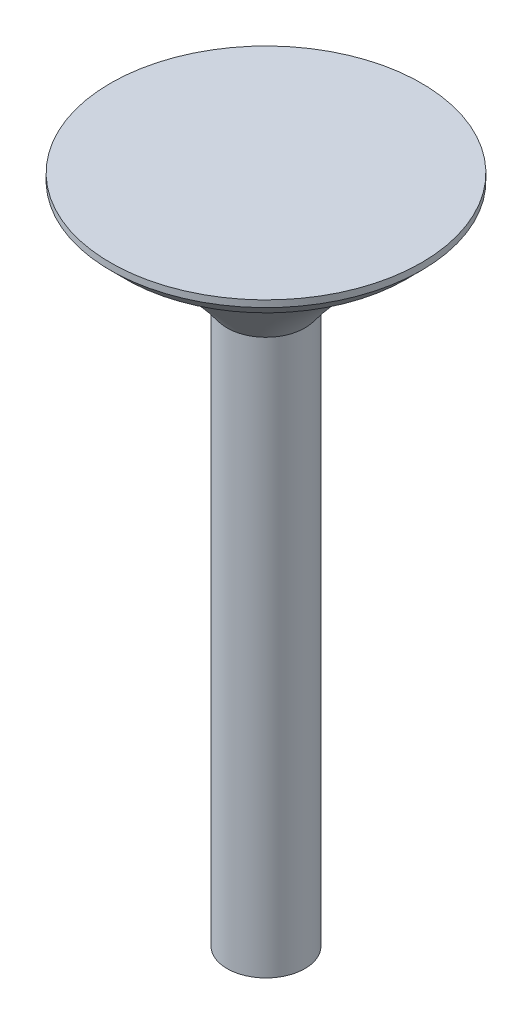
SolidWorks part; units mm, degrees
ref_plane "Front Plane" through (0, 0, 0) normal (0, 0, 1) x (1, 0, 0)
ref_plane "Top Plane" through (0, 0, 0) normal (0, 1, 0) x (1, 0, 0)
ref_plane "Right Plane" through (0, 0, 0) normal (1, 0, 0) x (0, 0, -1)
sketch "Sketch1" plane through (0, 0, 0) normal (0, 0, 1) x (1, 0, 0)
  line L0 (0, 105.7218) -> (0, 5.7218) construction
  line L1 (0, 105.7218) -> (-23.22, 105.7218)
  line L2 (-23.22, 105.7218) -> (-23.22, 104.7218)
  line L3 (-23.22, 104.7218) -> (-20.898, 102.3998)
  line L4 (0, 105.7218) -> (0, 5.7218)
  line L5 (-5.805, 88.5698) -> (-5.805, 5.7218)
  line L6 (-5.805, 5.7218) -> (0, 5.7218)
  arc A0 (-20.898, 102.3998) -> (-5.805, 88.5698) centre (-46.4154, 59.4014) cw
  point P9 (29.1197, 28.5755)
  point P10 (-5.805, 85.8991)
  point P11 (-20.2165, 101.7183)
  dimension "D7" = 50
  dimension "D2" = 23.22
  dimension "D3" = 1
  dimension "D4" = 45
  dimension "D1" = 5.805
  dimension "D6" = 100
  dimension "D5" = 2.322
  dimension "D8" = 16.152
revolve "Revolve1" add sketch "Sketch1" angle 360 about L0
equation "\"Valve Diameter\"= 46.44mm"
equation "\"Seat Angle Beta\"= 45deg"
equation "\"Seat Diameter\"= 41.796mm"
equation "\"Stem Diameter\"= 11.61mm"
equation "\"Seat Width\"= 2.322mm"
equation "\"Max Lift\"= 16.152mm"
equation "\"Overall Length\" = 100mm"
equation "\"Head Thickness\"= 1mm"
equation "\"D2@Sketch1\"=\"Valve Diameter\"/2"
equation "\"D3@Sketch1\"=\"Head Thickness\""
equation "\"D4@Sketch1\"=\"Seat Angle Beta\""
equation "\"D1@Sketch1\"=\"Stem Diameter\"/2"
equation "\"D6@Sketch1\"=\"Overall Length\""
equation "\"D5@Sketch1\"=\"Seat Width\""
equation "\"D8@Sketch1\"=\"Max Lift\""
